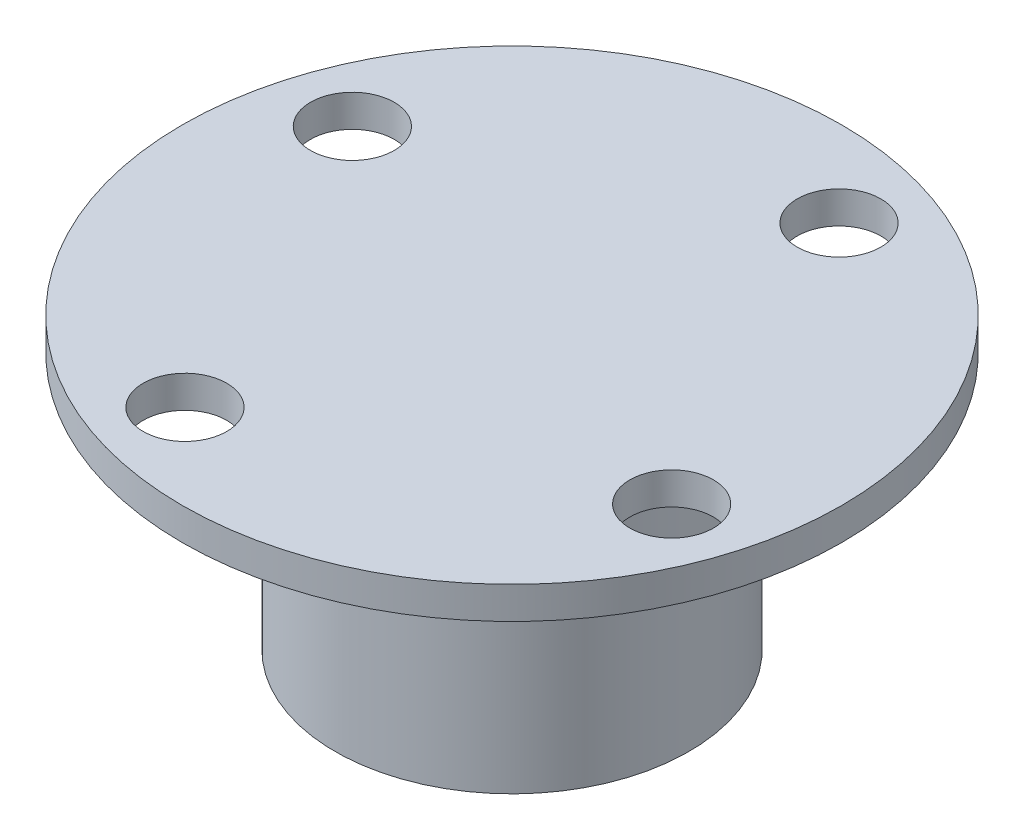
SolidWorks part; units mm, degrees
material "ABS"
ref_plane "Plan de face" through (0, 0, 0) normal (0, 0, 1) x (1, 0, 0)
ref_plane "Plan de dessus" through (0, 0, 0) normal (0, 1, 0) x (1, 0, 0)
ref_plane "Plan de droite" through (0, 0, 0) normal (1, 0, 0) x (0, 0, -1)
sketch "Esquisse1" plane through (0, -38.6013, 0) normal (0, -1, 0) x (1, 0, 0)
  circle A0 centre (14.0172, 17.25) radius 10.25
  arc A1 (9.5205, 8.039) -> (18.514, 26.461) centre (14.0172, 17.25) ccw construction
  dimension "D1" = 20.5
  dimension "D2" = 0
extrude "Boss.-Extru.1" add sketch "Esquisse1" along normal blind 1
hole_wizard "Dégagement M21" positions "Esquisse3" profile "Esquisse4" hole size "M2" standard "Ansi Metric" end condition up to next
sketch "Esquisse3" plane through (0, -39.6013, 0) normal (0, -1, 0) x (-1, 0, 0)
  circle A0 centre (-14.0172, -17.25) radius 8 construction
  point P0 (-11.4155, -24.8151)
  dimension "D1" = 16
sketch "Esquisse4" plane through (11.4155, -39.6013, 24.8151) normal (1, 0, 0) x (0, 0, -1)
  line L0 (0, 0) -> (0, 1.001)
  line L1 (0, 1.001) -> (1.3, 1.001)
  line L2 (1.3, 1.001) -> (1.3, 0)
  line L5 (1.3, 0) -> (0, 0)
  line L11 (0, -6.35) -> (0, 107.95) construction
  dimension "Diamètre du perçage jusqu'au prochain" = 2.6
  dimension "Profondeur du perçage jusqu'au prochain" = 1.001
pattern_circular "Répétition circulaire1" count 4 over 360 about axis through (14.0172, -39.6013, 17.25) along (0, -1, 0) of "Dégagement M21"
sketch "Esquisse9" plane through (0, -39.6013, 0) normal (0, -1, 0) x (-1, 0, 0)
  circle A0 centre (-14.0172, -17.25) radius 5.5
  dimension "D1" = 11
extrude "Boss.-Extru.4" add sketch "Esquisse9" along normal blind 8
sketch "Esquisse10" plane through (0, -47.6013, 0) normal (0, -1, 0) x (1, 0, 0)
  line L0 (11.9048, 19.85) -> (16.1297, 19.85)
  arc A0 (11.9048, 19.85) -> (16.1297, 19.85) centre (14.0172, 17.25) ccw
  dimension "D1" = 6.7
  dimension "D2" = 2.6
extrude "Enlèv. mat.-Extru.1" cut sketch "Esquisse10" against normal blind 6
fillet "Congé1" radius 0.5 1 edges at (14.0172, -39.6013, 11.75)
